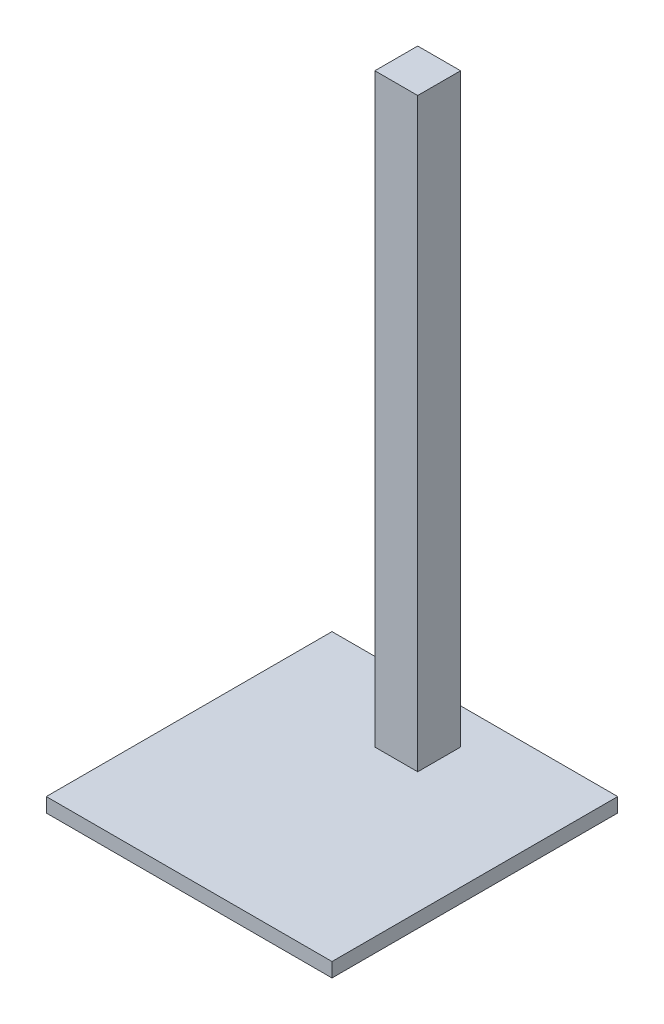
SolidWorks part; units mm, degrees
ref_plane "Front Plane" through (0, 0, 0) normal (0, 0, 1) x (1, 0, 0)
ref_plane "Top Plane" through (0, 0, 0) normal (0, 1, 0) x (1, 0, 0)
ref_plane "Right Plane" through (0, 0, 0) normal (1, 0, 0) x (0, 0, -1)
sketch "Sketch1" plane through (0, 0, 0) normal (0, 1, 0) x (1, 0, 0)
  line L1 (-25.4, -25.4) -> (25.4, -25.4)
  line L2 (-25.4, -25.4) -> (-25.4, 25.4)
  line L3 (-25.4, 25.4) -> (25.4, 25.4)
  line L4 (25.4, -25.4) -> (25.4, 25.4)
  line L5 (-25.4, -25.4) -> (25.4, 25.4) construction
  line L6 (-25.4, 25.4) -> (25.4, -25.4) construction
  point P0 (0, 0)
  dimension "D1" = 50.8
  dimension "D2" = 50.8
extrude "Boss-Extrude1" add sketch "Sketch1" along normal blind 2.54
sketch "Sketch2" plane through (0, 2.54, 0) normal (0, 1, 0) x (1, 0, 0)
  line L1 (-3.81, 19.05) -> (3.81, 19.05)
  line L2 (-3.81, 19.05) -> (-3.81, 11.43)
  line L3 (-3.81, 11.43) -> (3.81, 11.43)
  line L4 (3.81, 19.05) -> (3.81, 11.43)
  line L5 (-3.81, 19.05) -> (3.81, 11.43) construction
  line L6 (-3.81, 11.43) -> (3.81, 19.05) construction
  point P0 (0, 15.24)
  point P5 (0, 14.7034)
  dimension "D1" = 7.62
  dimension "D2" = 15.24
extrude "Boss-Extrude2" add sketch "Sketch2" along normal blind 104.14
